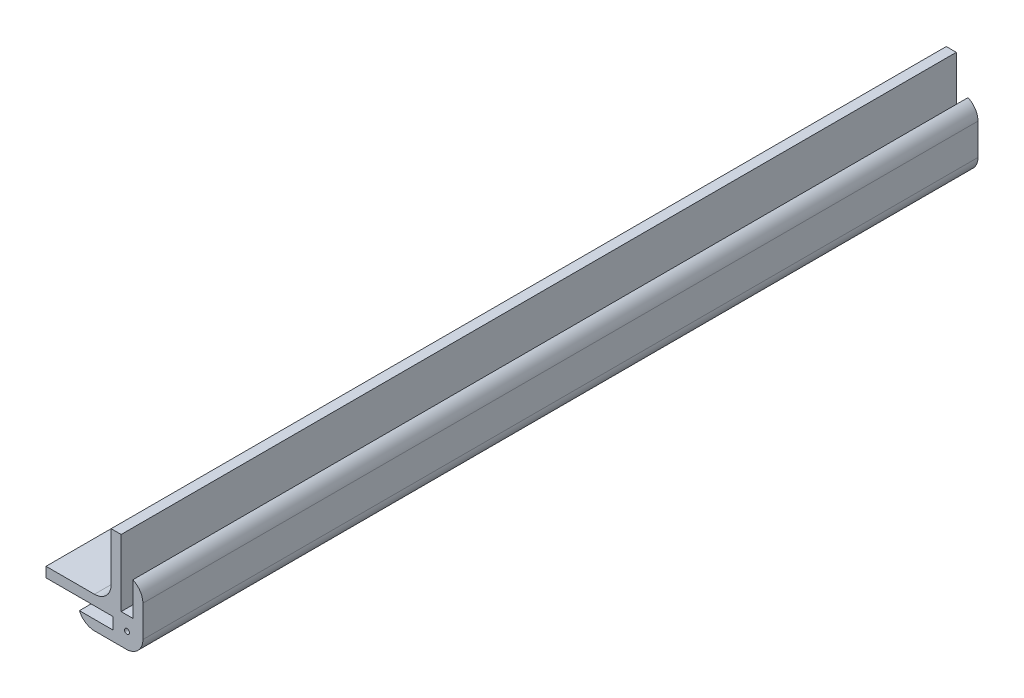
SolidWorks part; units mm, degrees
ref_plane "Front Plane" through (0, 0, 0) normal (0, 0, 1) x (1, 0, 0)
ref_plane "Top Plane" through (0, 0, 0) normal (0, 1, 0) x (1, 0, 0)
ref_plane "Right Plane" through (0, 0, 0) normal (1, 0, 0) x (0, 0, -1)
sketch "Sketch1" plane through (0, 0, 0) normal (0, 0, 1) x (1, 0, 0)
  line L0 (0, 0) -> (0, 16)
  line L1 (0, 16) -> (-3, 16)
  line L2 (-3, 16) -> (-3, 6)
  line L3 (-6.5, 6) -> (-3, 6)
  line L4 (-6.5, 6) -> (-6.5, 26)
  line L5 (-6.5, 26) -> (-9.5, 26)
  line L6 (-9.5, 26) -> (-9.5, 6.5)
  line L7 (-9.5, 6.5) -> (-29, 6.5)
  line L8 (-29, 6.5) -> (-29, 3.5)
  line L9 (-29, 3.5) -> (-9, 3.5)
  line L10 (-9, 3.5) -> (-9, 0)
  line L11 (-9, 0) -> (-19, 0)
  line L12 (-19, 0) -> (-19, -3)
  line L13 (-19, -3) -> (0, -3)
  line L14 (0, -3) -> (0, 0)
  dimension "D1" = 3.5
  dimension "D2" = 3.5
  dimension "D3" = 3
  dimension "D4" = 3
  dimension "D5" = 3
  dimension "D6" = 3
  dimension "D7" = 10
  dimension "D8" = 10
  dimension "D9" = 9
  dimension "D10" = 9
  dimension "D11" = 20
  dimension "D12" = 20
extrude "Boss-Extrude1" add sketch "Sketch1" along normal blind 250
fillet "Fillet1" radius 5 4 edges at (-9.5, 6.5, 125) (-19, -3, 125) (0, -3, 125) (0, 16, 125)
sketch "Sketch4" plane through (0, 0, 0) normal (0, 0, -1) x (-1, 0, 0)
  line L0 (4.75, 6) -> (4.75, 1.75) construction
  line L1 (3, 6) -> (6.5, 6) construction
  line L2 (9, 1.75) -> (4.75, 1.75) construction
  line L3 (9, 3.5) -> (9, 0) construction
  circle A0 centre (4.75, 1.75) radius 0.75
  dimension "D1" = 1.5
extrude "Cut-Extrude1" cut sketch "Sketch4" against normal blind 20
sketch "Sketch5" plane through (0, 0, 250) normal (0, 0, 1) x (1, 0, 0)
  line L0 (-4.75, 6) -> (-4.75, 1.75) construction
  line L2 (-9, 1.75) -> (-4.75, 1.75) construction
  line L4 (-3, 6) -> (-6.5, 6) construction
  line L6 (-9, 3.5) -> (-9, 0) construction
  circle A0 centre (-4.75, 1.75) radius 0.75
  dimension "D1" = 1.5
extrude "Cut-Extrude2" cut sketch "Sketch5" against normal blind 20
equation "\"ๅ\"=3.01294"
